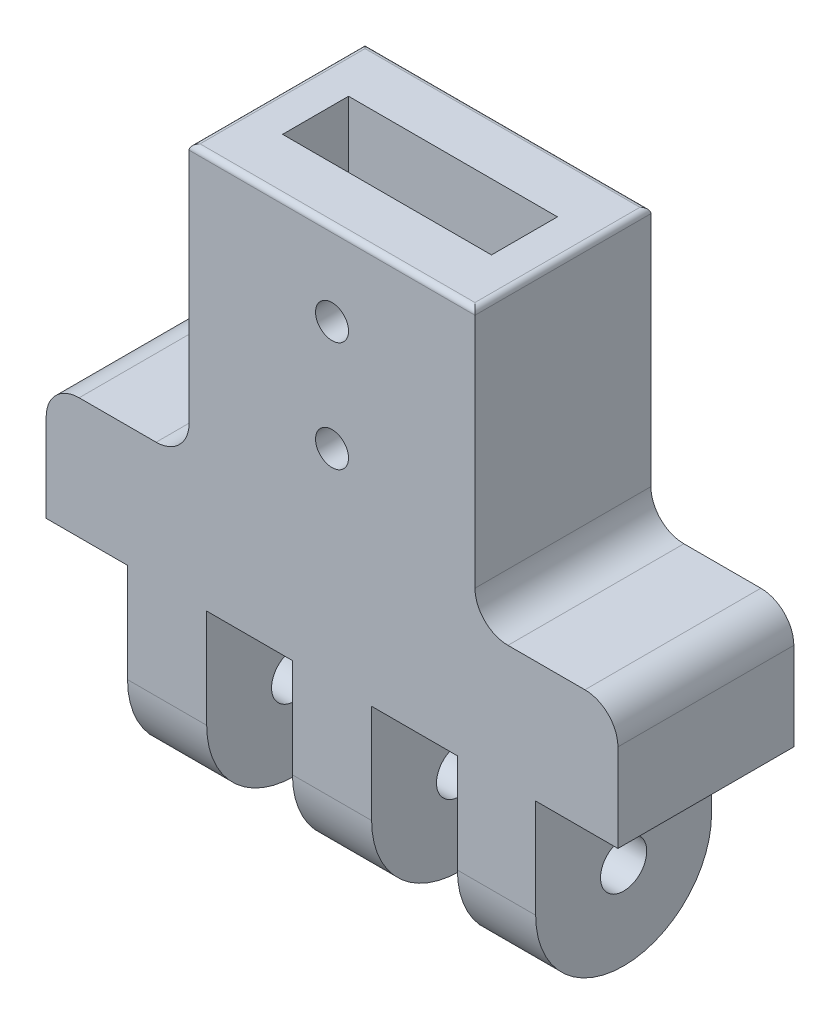
SolidWorks part; units mm, degrees
ref_plane "Front Plane" through (0, 0, 0) normal (0, 0, 1) x (1, 0, 0)
ref_plane "Top Plane" through (0, 0, 0) normal (0, 1, 0) x (1, 0, 0)
ref_plane "Right Plane" through (0, 0, 0) normal (1, 0, 0) x (0, 0, -1)
sketch "Sketch2" plane through (0, 0, 0) normal (1, 0, 0) x (0, 0, -1)
  line L2 (-8, 0) -> (-8, 20)
  line L3 (-8, 20) -> (8, 20)
  line L4 (8, 0) -> (8, 20)
  circle A0 centre (0, 0) radius 2.1
  arc A1 (-8, 0) -> (8, 0) centre (0, 0) ccw
  dimension "D1" = 16
  dimension "D2" = 4.2
  dimension "D3" = 20
extrude "Boss-Extrude1" add sketch "Sketch2" along normal mid plane 52
sketch "Sketch3" plane through (0, 0, 8) normal (0, 0, 1) x (1, 0, 0)
  line L0 (26, 0) -> (-26, 0) construction
  line L1 (-26, -9) -> (-18.6, -9)
  line L2 (-26, -9) -> (-26, 9)
  line L3 (-26, 9) -> (-18.6, 9)
  line L4 (-18.6, -9) -> (-18.6, 9)
  line L5 (-26, -9) -> (-18.6, 9) construction
  line L6 (-26, 9) -> (-18.6, -9) construction
  line L8 (-11.4, -9) -> (-3.6, -9)
  line L9 (-11.4, -9) -> (-11.4, 9)
  line L10 (-11.4, 9) -> (-3.6, 9)
  line L11 (-3.6, -9) -> (-3.6, 9)
  line L12 (-11.4, -9) -> (-3.6, 9) construction
  line L13 (-11.4, 9) -> (-3.6, -9) construction
  line L14 (3.6, -9) -> (11.4, -9)
  line L15 (3.6, -9) -> (3.6, 9)
  line L16 (3.6, 9) -> (11.4, 9)
  line L17 (11.4, -9) -> (11.4, 9)
  line L18 (3.6, -9) -> (11.4, 9) construction
  line L19 (3.6, 9) -> (11.4, -9) construction
  line L20 (-26, 20) -> (-26, 0) construction
  line L21 (26, 20) -> (26, 0) construction
  line L22 (18.519, -9) -> (26, -9)
  line L23 (18.519, -9) -> (18.519, 9)
  line L24 (18.519, 9) -> (26, 9)
  line L25 (26, -9) -> (26, 9)
  line L26 (18.519, -9) -> (26, 9) construction
  line L27 (18.519, 9) -> (26, -9) construction
  point P0 (-22.3, 0)
  point P7 (-7.5, 0)
  point P12 (7.5, 0)
  point P17 (-22.3, 9)
  point P20 (22.2595, 0)
  dimension "D1" = 9
  dimension "D4" = 7.2
  dimension "D6" = 7.2
  dimension "D2" = 7.8
  dimension "D3" = 14.6
extrude "Cut-Extrude1" cut sketch "Sketch3" against normal through all
ref_plane "Plane1" through (0, 20, 0) normal (0, 1, 0) x (1, 0, 0)
sketch "Sketch4" plane through (0, 20, 0) normal (0, 1, 0) x (1, 0, 0)
  line L0 (26, 8) -> (26, -8) construction
  line L1 (13, -8) -> (-13, -8)
  line L2 (13, -8) -> (13, 8)
  line L3 (13, 8) -> (-13, 8)
  line L4 (-13, -8) -> (-13, 8)
  line L5 (13, -8) -> (-13, 8) construction
  line L6 (13, 8) -> (-13, -8) construction
  line L8 (26, -8) -> (-26, -8) construction
  point P0 (0, 0)
  dimension "D1" = 26
  dimension "D2" = 16
  dimension "D3" = 26
extrude "Boss-Extrude2" add sketch "Sketch4" along normal blind 25
ref_plane "Plane2" through (0, 45, 0) normal (0, 1, 0) x (1, 0, 0)
sketch "Sketch5" plane through (0, 45, 0) normal (0, 1, 0) x (1, 0, 0)
  line L0 (13, -8) -> (13, 8) construction
  line L1 (-9.5, 3) -> (9.5, 3)
  line L2 (-9.5, 3) -> (-9.5, -3)
  line L3 (-9.5, -3) -> (9.5, -3)
  line L4 (9.5, 3) -> (9.5, -3)
  line L5 (-9.5, 3) -> (9.5, -3) construction
  line L6 (-9.5, -3) -> (9.5, 3) construction
  line L8 (-13, -8) -> (13, -8) construction
  line L10 (13, 8) -> (-13, 8) construction
  line L11 (13, -8) -> (13, 8) construction
  line L12 (-13, 8) -> (-13, -8) construction
  point P0 (0, 0)
  point P7 (0, -3.6435)
  point P8 (-9.6726, -4.8898)
  point P9 (0, 0)
  dimension "D1" = 19
  dimension "D2" = 13
  dimension "D3" = 6
  dimension "D4" = 5
  dimension "D5" = 5
extrude "Cut-Extrude2" cut sketch "Sketch5" against normal blind 25
fillet "Fillet2" radius 3 2 edges at (26, 20, 0) (-26, 20, 0)
sketch "Sketch6" plane through (0, 0, 0) normal (0, 0, 1) x (1, 0, 0)
  line L0 (9.5, 20) -> (9.5, 45) construction
  line L1 (-16.3932, 32.5) -> (15.2785, 32.5) construction
  line L2 (9.5, 20) -> (-9.5, 20) construction
  circle A0 centre (0, 37.5) radius 1.5
  circle A1 centre (0, 27.5) radius 1.5
  dimension "D1" = 3
  dimension "D2" = 9.5
  dimension "D3" = 10
  dimension "D4" = 5
  dimension "D5" = 12.5
extrude "Cut-Extrude3" cut sketch "Sketch6" against normal mid plane 25
fillet "Fillet3" radius 0.5 4 edges at (0, 45, 8) (13, 45, 0) (0, 45, -8) (-13, 45, 0)
fillet "Fillet4" radius 3 2 edges at (13, 20, 0) (-13, 20, 0)
equation "\"hingewidth\"=7.2"
equation "\"fingerwidth\"=10.5"
equation "\"gapwidth\"=7.4"
equation "\"D4@Sketch3\"=\"hingewidth\""
equation "\"D6@Sketch3\"=\"hingewidth\""
